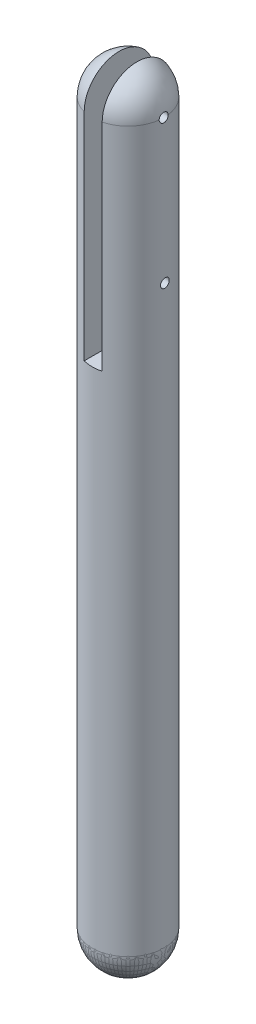
SolidWorks part; units mm, degrees
other "COLL.SPHERE-Tip"
material "1060 Alloy"
ref_plane "Front Plane" through (0, 0, 0) normal (0, 0, 1) x (1, 0, 0)
ref_plane "Top Plane" through (0, 0, 0) normal (0, 1, 0) x (1, 0, 0)
ref_plane "Right Plane" through (0, 0, 0) normal (1, 0, 0) x (0, 0, -1)
sketch "Sketch1" plane through (0, 0, 0) normal (0, 0, 1) x (1, 0, 0)
  line L0 (0, 100) -> (0, 110)
  line L1 (0, -100) -> (0, -110)
  line L2 (10, 100) -> (10, -100)
  line L4 (0, 100) -> (0, -100)
  arc A0 (10, 100) -> (0, 110) centre (0, 100) ccw
  arc A1 (0, -110) -> (10, -100) centre (0, -100) ccw
  dimension "D1" = 200
  dimension "D2" = 10
revolve "Revolve2" add sketch "Sketch1" angle 360 about L0
sketch "Sketch3" plane through (0, 0, 0) normal (0, 0, 1) x (1, 0, 0)
  line L1 (2.5, 110) -> (-2.5, 110)
  line L2 (2.5, 110) -> (2.5, 40)
  line L3 (2.5, 40) -> (-2.5, 40)
  line L4 (-2.5, 110) -> (-2.5, 40)
  arc A0 (10, 100) -> (-10, 100) centre (0, 100) ccw construction
  point P4 (0, 110)
  dimension "D1" = 70
  dimension "D2" = 5
extrude "Cut-Extrude2" cut sketch "Sketch3" against normal through all both and the other way through all
sketch "Sketch4" plane through (2.5, 0, 0) normal (-1, 0, 0) x (0, 0, 1)
  line L0 (9.6825, 40) -> (9.6825, 100) construction
  circle A0 centre (0, 100) radius 1.25
  arc A1 (9.6825, 100) -> (-9.6825, 100) centre (0, 100) ccw construction
  circle A2 centre (-0.3175, 60.0013) radius 1.25
  dimension "D1" = 2.5
  dimension "D2" = 2.5
  dimension "D3" = 40
  dimension "D4" = 10
extrude "Cut-Extrude3" cut sketch "Sketch4" against normal through all both and the other way through all
sketch "Sketch5" plane through (0, 0, 0) normal (0, 1, 0) x (1, 0, 0)
  circle A0 centre (0, 0) radius 10
ref_axis "Axis2" through (10, 100, 0) along (-1, 0, 0)
ref_point "Point1"
sketch "Sketch6" plane through (0, 0, 0) normal (0, 0, 1) x (1, 0, 0)
  line L0 (10, -100) -> (-10, -100) construction
  line L1 (0, -90) -> (0, -110)
  arc A0 (0, -110) -> (0, -90) centre (0, -100) ccw
  dimension "D1" = 20
ref_axis "Axis3" through (0, 100, 0) along (0, -1, 0)
revolve "Revolve4" add sketch "Sketch6" angle 360 about L1
ref_axis "Axis4" through (10.3724, 60.0013, -0.3175) along (-1, 0, 0)
ref_point "Point2"
